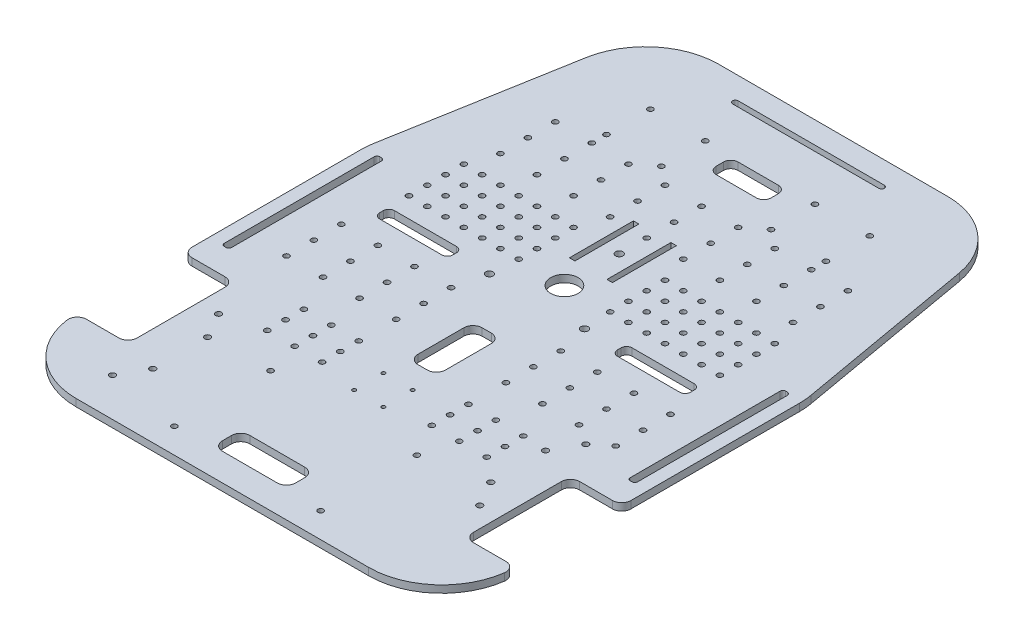
SolidWorks part; units mm, degrees
ref_plane "前视基准面" through (0, 0, 0) normal (0, 0, 1) x (1, 0, 0)
ref_plane "上视基准面" through (0, 0, 0) normal (0, 1, 0) x (1, 0, 0)
ref_plane "右视基准面" through (0, 0, 0) normal (1, 0, 0) x (0, 0, -1)
other "Configuration Table"
sketch "草图1" plane through (0, 0, 0) normal (0, 1, 0) x (1, 0, 0)
  line L1 (-120, -167) -> (120, -167)
  line L2 (-120, -167) -> (-120, 167)
  line L3 (-120, 167) -> (120, 167)
  line L4 (120, -167) -> (120, 167)
  line L5 (-120, -167) -> (120, 167) construction
  line L6 (-120, 167) -> (120, -167) construction
  point P0 (0, 0)
  dimension "D1" = 334
  dimension "D2" = 240
extrude "凸台-拉伸1" add sketch "草图1" along normal blind 4
sketch "草图2" plane through (0, 4, 0) normal (0, 1, 0) x (1, 0, 0)
  line L0 (-120, 32) -> (-96.1959, 167)
  line L1 (-120, 167) -> (-120, -167) construction
  line L2 (120, 167) -> (-120, 167) construction
  line L3 (-96.1959, 167) -> (-120, 167)
  line L4 (-120, 167) -> (-120, 32)
  line L5 (0, 0) -> (0, 167) construction
  line L6 (120, 167) -> (120, 32)
  line L7 (96.1959, 167) -> (120, 167)
  line L8 (120, 32) -> (96.1959, 167)
  dimension "D1" = 10
  dimension "D2" = 135
extrude "切除-拉伸1" cut sketch "草图2" against normal blind 4
fillet "圆角1" radius 40 6 edges at (120, 2, -32) (96.1959, 2, -167) (120, 2, 167) (-120, 2, 167) (-120, 2, -32) (-96.1959, 2, -167)
sketch "草图3" plane through (0, 4, 0) normal (0, 1, 0) x (1, 0, 0)
  line L0 (-73.1222, -102) -> (-73.1222, -132) construction
  line L1 (-120, 28.5005) -> (-120, -127) construction
  line L2 (-80, -167) -> (80, -167) construction
  circle A0 centre (-81.1222, -88) radius 1.6
  circle A1 centre (-73.1222, -102) radius 1.6
  circle A2 centre (-73.1222, -132) radius 1.6
  circle A3 centre (-81.1222, -146) radius 1.6
  point P2 (-73.1222, -117)
  dimension "D1" = 3.2
  dimension "D2" = 8
  dimension "D3" = 14
  dimension "D4" = 30
  dimension "D5" = 8
  dimension "D6" = 14
  dimension "D7" = 46.8778
  dimension "D8" = 50
extrude "切除-拉伸2" cut sketch "草图3" against normal blind 10
sketch "草图6" plane through (0, 4, 0) normal (0, 1, 0) x (1, 0, 0)
  line L0 (92, -126.65) -> (120, -126.65)
  line L1 (92, -126.65) -> (92, -68.65)
  line L2 (92, -68.65) -> (120, -68.65)
  line L3 (120, -126.65) -> (120, -68.65)
  line L4 (92, -126.65) -> (120, -68.65) construction
  line L5 (92, -68.65) -> (120, -126.65) construction
  line L6 (0, -97.65) -> (0, 59.0833) construction
  line L7 (-120, -126.65) -> (-92, -126.65)
  line L8 (-106, -97.65) -> (106, -97.65) construction
  line L9 (-73.1222, -132) -> (-73.1222, -102) construction
  line L10 (-120, -126.65) -> (-120, -68.65)
  line L11 (-120, -68.65) -> (-92, -68.65)
  line L12 (-92, -126.65) -> (-92, -68.65)
  line L13 (-120, -126.65) -> (-92, -68.65) construction
  line L14 (-120, -68.65) -> (-92, -126.65) construction
  line L15 (120, -127) -> (120, 28.5005) construction
  point P0 (106, -97.65)
  point P11 (-73.1222, -117)
  dimension "D1" = 28
  dimension "D2" = 58
  dimension "D3" = 58
  dimension "D4" = 28
  dimension "D5" = 19.35
extrude "切除-拉伸4" cut sketch "草图6" against normal blind 10
fillet "圆角2" radius 5 8 edges at (92, 2, 126.65) (92, 2, 68.65) (120, 2, 68.65) (120, 2, 126.65) (-120, 2, 126.65) (-92, 2, 126.65) (-92, 2, 68.65) (-120, 2, 68.65)
sketch "草图4" plane through (0, 4, 0) normal (0, 1, 0) x (1, 0, 0)
  line L0 (120, -63.65) -> (120, 28.5005) construction
  line L1 (73.0185, -63.3) -> (73.0185, -93.3) construction
  line L2 (83.3206, -97.65) -> (-92, -97.65) construction
  line L3 (-92, -121.65) -> (-92, -73.65) construction
  circle A0 centre (81.0185, -49.3) radius 1.6
  circle A1 centre (73.0185, -63.3) radius 1.6
  circle A2 centre (73.0185, -93.3) radius 1.6
  circle A3 centre (81.0185, -107.3) radius 1.6
  circle A6 centre (-73.1222, -132) radius 1.6 construction
  circle A7 centre (-73.1222, -102) radius 1.6 construction
  circle A8 centre (-73.1222, -132) radius 1.6
  circle A9 centre (-73.1222, -102) radius 1.6
  point P2 (73.0185, -78.3)
  dimension "D1" = 3.2
  dimension "D2" = 14
  dimension "D3" = 30
  dimension "D4" = 14
  dimension "D5" = 8
  dimension "D6" = 19.35
  dimension "D7" = 46.9815
extrude "切除-拉伸3" cut sketch "草图4" against normal blind 10
sketch "草图8" plane through (0, 4, 0) normal (0, 1, 0) x (1, 0, 0)
  line L0 (0, 0) -> (0, -153.7962) construction
  line L1 (-60, 127) -> (-30, 127) construction
  line L2 (-60, 127) -> (-60, 103) construction
  line L3 (-60, 103) -> (-30, 103) construction
  line L4 (-30, 127) -> (-30, 103) construction
  line L5 (-60, 127) -> (-30, 103) construction
  line L6 (-60, 103) -> (-30, 127) construction
  line L7 (60, 127) -> (30, 127) construction
  line L8 (30, 127) -> (30, 103) construction
  line L9 (60, 103) -> (30, 103) construction
  line L10 (60, 127) -> (60, 103) construction
  line L11 (62.6319, 167) -> (-62.6319, 167) construction
  circle A0 centre (-60, 127) radius 1.5
  circle A1 centre (-30, 127) radius 1.5
  circle A2 centre (-60, 103) radius 1.5
  circle A3 centre (-30, 103) radius 1.5
  circle A4 centre (30, 127) radius 1.5
  circle A5 centre (30, 103) radius 1.5
  circle A6 centre (60, 127) radius 1.5
  circle A7 centre (60, 103) radius 1.5
  point P0 (-45, 115)
  dimension "D4" = 3
  dimension "D1" = 30
  dimension "D2" = 24
  dimension "D3" = 45
  dimension "D5" = 40
extrude "切除-拉伸5" cut sketch "草图8" against normal blind 10
sketch "草图9" plane through (0, 4, 0) normal (0, 1, 0) x (1, 0, 0)
  line L0 (0, -79) -> (0, 0) construction
  line L1 (-8, -71) -> (8, -71) construction
  line L2 (-8, -71) -> (-8, -87) construction
  line L3 (-8, -87) -> (8, -87) construction
  line L4 (8, -71) -> (8, -87) construction
  line L5 (-8, -71) -> (8, -87) construction
  line L6 (-8, -87) -> (8, -71) construction
  line L7 (-80, -167) -> (80, -167) construction
  circle A0 centre (-8, -71) radius 1
  circle A1 centre (8, -71) radius 1
  circle A2 centre (-8, -87) radius 1
  circle A3 centre (8, -87) radius 1
  point P0 (0, -79)
  dimension "D4" = 2
  dimension "D1" = 16
  dimension "D2" = 16
  dimension "D3" = 80
extrude "切除-拉伸6" cut sketch "草图9" against normal blind 10
sketch "草图11" plane through (0, 4, 0) normal (0, 1, 0) x (1, 0, 0)
  line L0 (0, 0) -> (0, 20) construction
  line L1 (0, 50) -> (-25.9808, 5) construction
  line L2 (-25.9808, 5) -> (25.9808, 5) construction
  circle A0 centre (0, 50) radius 2
  circle A1 centre (0, 20) radius 30 construction
  circle A2 centre (25.9808, 5) radius 2
  circle A3 centre (-25.9808, 5) radius 2
  circle A4 centre (0, 20) radius 7.5
  dimension "D1" = 60
  dimension "D3" = 4
  dimension "D5" = 15
  dimension "D2" = 20
  dimension "D4" = 30
extrude "切除-拉伸7" cut sketch "草图11" against normal blind 10
sketch "草图12" plane through (0, 4, 0) normal (0, 1, 0) x (1, 0, 0)
  line L0 (-40, -153.309) -> (40, -153.309) construction
  line L1 (-40, -153.309) -> (-40, -100.691) construction
  line L2 (-40, -100.691) -> (40, -100.691) construction
  line L3 (40, -153.309) -> (40, -100.691) construction
  line L4 (-40, -153.309) -> (40, -100.691) construction
  line L5 (-40, -100.691) -> (40, -153.309) construction
  line L7 (-80, -167) -> (80, -167) construction
  circle A0 centre (40, -100.691) radius 1.5
  circle A1 centre (40, -153.309) radius 1.5
  circle A2 centre (-40, -100.691) radius 1.5
  circle A3 centre (-40, -153.309) radius 1.5
  point P0 (0, -127)
  dimension "D5" = 3
  dimension "D1" = 80
  dimension "D2" = 52.618
  dimension "D3" = 127
  dimension "D4" = 40
extrude "切除-拉伸8" cut sketch "草图12" against normal blind 10
sketch "草图13" plane through (0, 4, 0) normal (0, 1, 0) x (1, 0, 0)
  line L0 (-40, 153.5) -> (40, 153.5) construction
  line L1 (-40, 155) -> (40, 155)
  line L2 (-40, 152) -> (40, 152)
  line L3 (62.6319, 167) -> (-62.6319, 167) construction
  arc A0 (-40, 155) -> (-40, 152) centre (-40, 153.5) ccw
  arc A1 (40, 152) -> (40, 155) centre (40, 153.5) ccw
  point P2 (0, 153.5)
  dimension "D1" = 3
  dimension "D2" = 80
  dimension "D3" = 12
extrude "切除-拉伸9" cut sketch "草图13" against normal blind 10
sketch "草图14" plane through (0, 4, 0) normal (0, 1, 0) x (1, 0, 0)
  line L1 (-20, -137) -> (20, -137)
  line L2 (-20, -137) -> (-20, -152)
  line L3 (-20, -152) -> (20, -152)
  line L4 (20, -137) -> (20, -152)
  line L5 (-20, -137) -> (20, -152) construction
  line L6 (-20, -152) -> (20, -137) construction
  line L7 (-80, -167) -> (80, -167) construction
  point P0 (0, -144.5)
  dimension "D1" = 40
  dimension "D2" = 15
  dimension "D3" = 15
extrude "切除-拉伸10" cut sketch "草图14" against normal blind 10
fillet "圆角3" radius 5 4 edges at (20, 2, 152) (-20, 2, 152) (20, 2, 137) (-20, 2, 137)
sketch "草图16" plane through (0, 4, 0) normal (0, 1, 0) x (1, 0, 0)
  line L0 (0, 0) -> (0, 75.4066) construction
  line L1 (-120, 28.5005) -> (-120, -63.65) construction
  line L2 (-113, -54.5) -> (-109, -54.5)
  line L3 (-113, -54.5) -> (-113, 30.5)
  line L4 (-113, 30.5) -> (-109, 30.5)
  line L5 (-109, -54.5) -> (-109, 30.5)
  line L6 (-113, -54.5) -> (-109, 30.5) construction
  line L7 (-113, 30.5) -> (-109, -54.5) construction
  point P3 (-111, -12)
  dimension "D1" = 4
  dimension "D2" = 111.6468
  dimension "D3" = 85
  dimension "D4" = 12
  dimension "D5" = 7
extrude "切除-拉伸11" cut sketch "草图16" against normal blind 10
fillet "圆角4" radius 1.5 4 edges at (-109, 2, 54.5) (-113, 2, 54.5) (-113, 2, -30.5) (-109, 2, -30.5)
mirror "镜向1" about plane through (0, 0, 0) normal (1, 0, 0) of "切除-拉伸11", "圆角4"
sketch "草图17" plane through (0, 4, 0) normal (0, 1, 0) x (1, 0, 0)
  line L0 (-60, -82.5) -> (-15.0419, -82.5) construction
  line L1 (-60, -82.5) -> (-60, 0.095) construction
  circle A0 centre (-60, -82.5) radius 1.5
  circle A1 centre (-45, -82.5) radius 1.5
  circle A2 centre (-30, -82.5) radius 1.5
  circle A4 centre (-45, -72.5) radius 1.5
  circle A5 centre (-30, -72.5) radius 1.5
  circle A7 centre (-45, -62.5) radius 1.5
  circle A8 centre (-30, -62.5) radius 1.5
  circle A10 centre (-60, -72.5) radius 1.5
  circle A11 centre (-60, -62.5) radius 1.5
  dimension "D1" = 82.5
  dimension "D3" = 3
  dimension "D4" = 3
  dimension "D2" = 60
  dimension "D6" = 15
  dimension "D7" = 10
  dimension "D5" = 3
extrude "切除-拉伸12" cut sketch "草图17" against normal blind 10
mirror "镜向2" about plane through (0, 0, 0) normal (1, 0, 0) of "切除-拉伸12"
sketch "草图18" plane through (0, 4, 0) normal (0, 1, 0) x (1, 0, 0)
  line L0 (-90, -42) -> (-18.0925, -42) construction
  line L1 (-90, -42) -> (-90, -6.3856) construction
  line L2 (0, 0) -> (0, -52.3131) construction
  circle A0 centre (-90, -42) radius 1.5
  circle A1 centre (-70, -42) radius 1.5
  circle A2 centre (-50, -42) radius 1.5
  circle A3 centre (-30, -42) radius 1.5
  circle A4 centre (-10, -42) radius 1.5 construction
  circle A5 centre (10, -42) radius 1.5 construction
  circle A6 centre (30, -42) radius 1.5
  circle A7 centre (50, -42) radius 1.5
  circle A8 centre (70, -42) radius 1.5
  circle A9 centre (90, -42) radius 1.5
  circle A10 centre (-70, -27) radius 1.5
  circle A11 centre (-50, -27) radius 1.5
  circle A12 centre (-30, -27) radius 1.5
  circle A13 centre (-10, -27) radius 1.5 construction
  circle A14 centre (10, -27) radius 1.5 construction
  circle A15 centre (30, -27) radius 1.5
  circle A16 centre (50, -27) radius 1.5
  circle A17 centre (70, -27) radius 1.5
  circle A18 centre (90, -27) radius 1.5
  circle A19 centre (-70, -12) radius 1.5
  circle A20 centre (-50, -12) radius 1.5
  circle A21 centre (-30, -12) radius 1.5
  circle A22 centre (-10, -12) radius 1.5 construction
  circle A23 centre (10, -12) radius 1.5 construction
  circle A24 centre (30, -12) radius 1.5
  circle A25 centre (50, -12) radius 1.5
  circle A26 centre (70, -12) radius 1.5
  circle A27 centre (90, -12) radius 1.5
  circle A28 centre (-90, -27) radius 1.5
  circle A29 centre (-90, -12) radius 1.5
  dimension "D1" = 3
  dimension "D2" = 3
  dimension "D5" = 10
  dimension "D3" = 42
  dimension "D4" = 90
  dimension "D7" = 15
  dimension "D8" = 20
  dimension "D6" = 3
extrude "切除-拉伸13" cut sketch "草图18" against normal blind 10
sketch "草图19" plane through (0, 4, 0) normal (0, 1, 0) x (1, 0, 0)
  line L0 (-85, 20) -> (-13.8548, 20) construction
  line L1 (-85, 20) -> (-85, 76.2494) construction
  line L2 (0, 0) -> (0, 125.095) construction
  circle A0 centre (-85, 20) radius 1.5
  circle A1 centre (-75, 20) radius 1.5
  circle A2 centre (-65, 20) radius 1.5
  circle A3 centre (-55, 20) radius 1.5
  circle A4 centre (-45, 20) radius 1.5
  circle A5 centre (-35, 20) radius 1.5
  circle A6 centre (-25, 20) radius 1.5
  circle A7 centre (-75, 30) radius 1.5
  circle A8 centre (-65, 30) radius 1.5
  circle A9 centre (-55, 30) radius 1.5
  circle A10 centre (-45, 30) radius 1.5
  circle A11 centre (-35, 30) radius 1.5
  circle A12 centre (-25, 30) radius 1.5
  circle A13 centre (-75, 40) radius 1.5
  circle A14 centre (-65, 40) radius 1.5
  circle A15 centre (-55, 40) radius 1.5
  circle A16 centre (-45, 40) radius 1.5
  circle A17 centre (-35, 40) radius 1.5
  circle A18 centre (-25, 40) radius 1.5
  circle A19 centre (-75, 50) radius 1.5
  circle A20 centre (-65, 50) radius 1.5
  circle A21 centre (-55, 50) radius 1.5
  circle A22 centre (-45, 50) radius 1.5
  circle A23 centre (-35, 50) radius 1.5
  circle A24 centre (-25, 50) radius 1.5
  circle A37 centre (-85, 30) radius 1.5
  circle A38 centre (-85, 40) radius 1.5
  circle A39 centre (-85, 50) radius 1.5
  circle A41 centre (85, 50) radius 1.5
  circle A42 centre (85, 40) radius 1.5
  circle A43 centre (85, 30) radius 1.5
  circle A44 centre (25, 50) radius 1.5
  circle A45 centre (35, 50) radius 1.5
  circle A46 centre (45, 50) radius 1.5
  circle A47 centre (55, 50) radius 1.5
  circle A48 centre (65, 50) radius 1.5
  circle A49 centre (75, 50) radius 1.5
  circle A50 centre (25, 40) radius 1.5
  circle A51 centre (35, 40) radius 1.5
  circle A52 centre (45, 40) radius 1.5
  circle A53 centre (55, 40) radius 1.5
  circle A54 centre (65, 40) radius 1.5
  circle A55 centre (75, 40) radius 1.5
  circle A56 centre (25, 30) radius 1.5
  circle A57 centre (35, 30) radius 1.5
  circle A58 centre (45, 30) radius 1.5
  circle A59 centre (55, 30) radius 1.5
  circle A60 centre (65, 30) radius 1.5
  circle A61 centre (75, 30) radius 1.5
  circle A62 centre (25, 20) radius 1.5
  circle A63 centre (35, 20) radius 1.5
  circle A64 centre (45, 20) radius 1.5
  circle A65 centre (55, 20) radius 1.5
  circle A66 centre (65, 20) radius 1.5
  circle A67 centre (75, 20) radius 1.5
  circle A68 centre (85, 20) radius 1.5
  dimension "D1" = 3
  dimension "D4" = 7
  dimension "D2" = 20
  dimension "D3" = 85
  dimension "D6" = 10
  dimension "D7" = 10
  dimension "D5" = 4
extrude "切除-拉伸14" cut sketch "草图19" against normal through all
sketch "草图20" plane through (0, 4, 0) normal (0, 1, 0) x (1, 0, 0)
  line L0 (0, 0) -> (0, 5) construction
  line L1 (0, 5) -> (-65, 5) construction
  line L2 (85, 1) -> (45, 1)
  line L3 (-85, 9) -> (-45, 9)
  line L4 (-85, 9) -> (-85, 1)
  line L5 (-85, 1) -> (-45, 1)
  line L6 (-45, 9) -> (-45, 1)
  line L7 (-85, 9) -> (-45, 1) construction
  line L8 (-85, 1) -> (-45, 9) construction
  line L9 (45, 9) -> (45, 1)
  line L10 (85, 9) -> (45, 9)
  line L11 (85, 9) -> (85, 1)
  dimension "D1" = 5
  dimension "D2" = 65
  dimension "D3" = 40
  dimension "D4" = 8
extrude "切除-拉伸15" cut sketch "草图20" against normal through all
fillet "圆角5" radius 3 8 edges at (45, 2, -1) (45, 2, -9) (85, 2, -9) (85, 2, -1) (-45, 2, -1) (-85, 2, -1) (-45, 2, -9) (-85, 2, -9)
sketch "草图21" plane through (0, 4, 0) normal (0, 1, 0) x (1, 0, 0)
  line L0 (0, 0) -> (0, -40) construction
  line L2 (-7.5, -22.5) -> (7.5, -22.5)
  line L3 (-7.5, -22.5) -> (-7.5, -57.5)
  line L4 (-7.5, -57.5) -> (7.5, -57.5)
  line L5 (7.5, -22.5) -> (7.5, -57.5)
  line L6 (-7.5, -22.5) -> (7.5, -57.5) construction
  line L7 (-7.5, -57.5) -> (7.5, -22.5) construction
  dimension "D1" = 40
  dimension "D2" = 35
  dimension "D3" = 15
extrude "切除-拉伸16" cut sketch "草图21" against normal through all
fillet "圆角6" radius 5 4 edges at (7.5, 2, 57.5) (-7.5, 2, 57.5) (-7.5, 2, 22.5) (7.5, 2, 22.5)
sketch "草图22" plane through (0, 4, 0) normal (0, 1, 0) x (1, 0, 0)
  line L0 (-80, 65) -> (53.898, 65) construction
  line L1 (-80, 65) -> (-80, 112.5522) construction
  circle A0 centre (-80, 65) radius 1.5
  circle A1 centre (-60, 65) radius 1.5
  circle A2 centre (-40, 65) radius 1.5
  circle A3 centre (-20, 65) radius 1.5
  circle A4 centre (0, 65) radius 1.5
  circle A5 centre (20, 65) radius 1.5
  circle A6 centre (40, 65) radius 1.5
  circle A7 centre (60, 65) radius 1.5
  circle A8 centre (80, 65) radius 1.5
  circle A9 centre (-60, 80) radius 1.5
  circle A10 centre (-40, 80) radius 1.5
  circle A11 centre (-20, 80) radius 1.5
  circle A12 centre (0, 80) radius 1.5
  circle A13 centre (20, 80) radius 1.5
  circle A14 centre (40, 80) radius 1.5
  circle A15 centre (60, 80) radius 1.5
  circle A16 centre (80, 80) radius 1.5
  circle A17 centre (-60, 95) radius 1.5
  circle A18 centre (-40, 95) radius 1.5
  circle A19 centre (-20, 95) radius 1.5
  circle A20 centre (0, 95) radius 1.5
  circle A21 centre (20, 95) radius 1.5
  circle A22 centre (40, 95) radius 1.5
  circle A23 centre (60, 95) radius 1.5
  circle A24 centre (80, 95) radius 1.5
  circle A25 centre (-80, 80) radius 1.5
  circle A26 centre (-80, 95) radius 1.5
  dimension "D1" = 65
  dimension "D3" = 3
  dimension "D4" = 9
  dimension "D2" = 80
  dimension "D6" = 15
  dimension "D7" = 20
  dimension "D5" = 3
extrude "切除-拉伸17" cut sketch "草图22" against normal through all
sketch "草图23" plane through (0, 4, 0) normal (0, 1, 0) x (1, 0, 0)
  line L1 (-15, 114) -> (15, 114)
  line L2 (-15, 114) -> (-15, 126)
  line L3 (-15, 126) -> (15, 126)
  line L4 (15, 114) -> (15, 126)
  line L5 (-15, 114) -> (15, 126) construction
  line L6 (-15, 126) -> (15, 114) construction
  point P0 (0, 120)
  dimension "D1" = 12
  dimension "D2" = 30
  dimension "D3" = 120
extrude "切除-拉伸18" cut sketch "草图23" against normal through all
fillet "圆角7" radius 4 4 edges at (15, 2, -114) (15, 2, -126) (-15, 2, -114) (-15, 2, -126)
sketch "草图24" plane through (0, 4, 0) normal (0, 1, 0) x (1, 0, 0)
  line L0 (0, 0) -> (0, 80) construction
  line L1 (-11.75, 34.5) -> (-8.75, 34.5)
  line L2 (-11.75, 34.5) -> (-11.75, 69.5)
  line L3 (-11.75, 69.5) -> (-8.75, 69.5)
  line L4 (-8.75, 34.5) -> (-8.75, 69.5)
  line L5 (-11.75, 34.5) -> (-8.75, 69.5) construction
  line L6 (-11.75, 69.5) -> (-8.75, 34.5) construction
  line L7 (11.75, 69.5) -> (8.75, 69.5)
  line L8 (11.75, 34.5) -> (11.75, 69.5)
  line L9 (11.75, 34.5) -> (8.75, 34.5)
  line L10 (8.75, 34.5) -> (8.75, 69.5)
  point P0 (-10.25, 52)
  dimension "D1" = 3
  dimension "D2" = 35
  dimension "D3" = 17.5
  dimension "D4" = 52
extrude "切除-拉伸19" cut sketch "草图24" against normal through all
